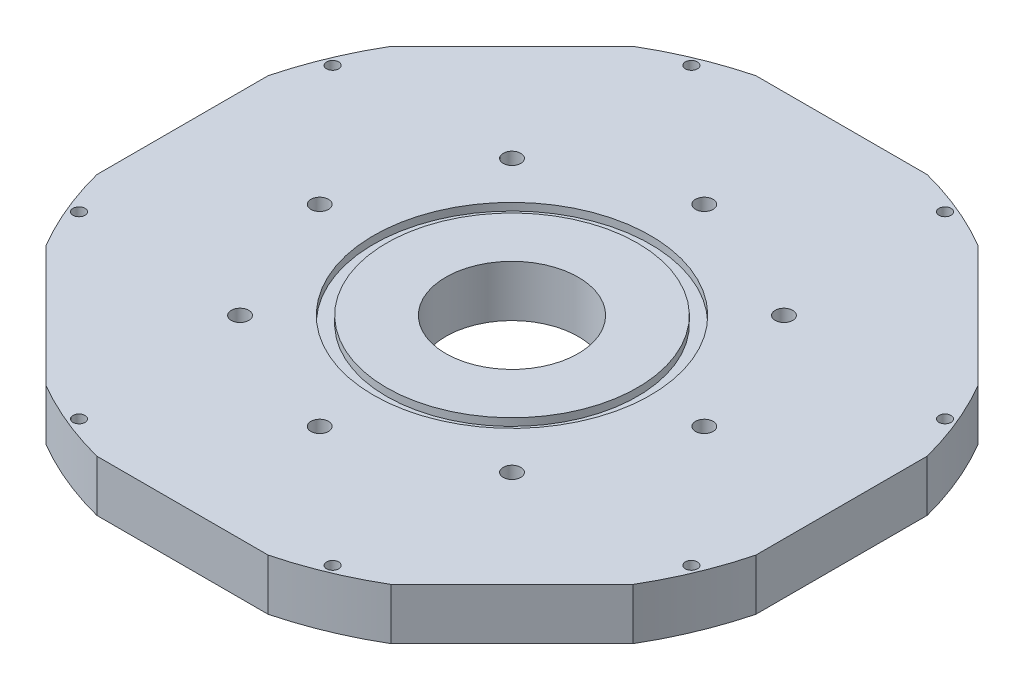
SolidWorks part; units mm, degrees
material "6061-T4 (SS)"
ref_plane "Front Plane" through (0, 0, 0) normal (0, 0, 1) x (1, 0, 0)
ref_plane "Top Plane" through (0, 0, 0) normal (0, 1, 0) x (1, 0, 0)
ref_plane "Right Plane" through (0, 0, 0) normal (1, 0, 0) x (0, 0, -1)
sketch "Sketch1" plane through (0, 0, 0) normal (0, 1, 0) x (1, 0, 0)
  line L1 (-50.6583, 122.3) -> (-122.3, 50.6583)
  line L2 (-122.3, 50.6583) -> (-122.3, -50.6583)
  line L3 (-122.3, -50.6583) -> (-50.6583, -122.3)
  line L4 (-50.6583, -122.3) -> (50.6583, -122.3)
  line L5 (50.6583, -122.3) -> (122.3, -50.6583)
  line L6 (122.3, -50.6583) -> (122.3, 50.6583)
  line L7 (122.3, 50.6583) -> (50.6583, 122.3)
  line L8 (50.6583, 122.3) -> (-50.6583, 122.3)
  circle A0 centre (0, 0) radius 122.3 construction
  circle A1 centre (0, 0) radius 126.365
  dimension "D2" = 252.73
  dimension "D1" = 244.6
extrude "Boss-Extrude1" add sketch "Sketch1" along normal blind 19.05 contours L4 A1 L5 L6 L7 L8 L1 L2 L3 region at (0, 0, 0)
sketch "Sketch3" plane through (0, 19.05, 0) normal (0, 1, 0) x (1, 0, 0)
  circle A0 centre (0, 0) radius 24.5745
  dimension "D1" = 49.149
extrude "Cut-Extrude1" cut sketch "Sketch3" against normal through all contours A0
sketch "Sketch5" plane through (0, 19.05, 0) normal (0, 1, 0) x (1, 0, 0)
  circle A0 centre (0, 0) radius 46.5455
  circle A1 centre (0, 0) radius 51.3715
  dimension "D1" = 93.091
  dimension "D2" = 102.743
extrude "Cut-Extrude2" cut sketch "Sketch5" against normal blind 2.794
sketch "Sketch19" plane through (0, 19.05, 0) normal (0, 1, 0) x (1, 0, 0)
  line L5 (-63.9978, 108.9605) -> (-31.7934, 122.3) construction
  line L6 (-47.8956, 115.6303) -> (-43.6974, 105.4949) construction
  circle A4 centre (0, 0) radius 122.9995
  circle A5 centre (-47.0699, 113.6367) radius 2.2479
  dimension "D1" = 4.4958
  dimension "D3" = 245.999
extrude "Cut-Extrude4" cut sketch "Sketch19" against normal through all contours A4 A5 | A4 A5 region at (-46.7034, 19.05, -112.7519) region at (-47.4335, 19.05, -114.5147)
pattern_circular "CirPattern2" count 8 over 360 about axis through (0, 0, 0) along (0, 1, 0) of "Cut-Extrude4"
sketch "Sketch21" plane through (0, 19.05, 0) normal (0, 1, 0) x (1, 0, 0)
  point P0 (-71.374, 0)
  dimension "D1" = 71.374
hole_wizard "5/16-18 Tapped Hole2" positions "Sketch22" profile "Sketch23" tap size "5/16-18" standard "ANSI Inch"
sketch "Sketch22" plane through (0, 19.05, 0) normal (0, 1, 0) x (1, 0, 0)
  point P0 (-71.374, 0)
sketch "Sketch23" plane through (-71.374, 19.05, 0) normal (1, 0, 0) x (0, 0, 1)
  line L0 (0, 0) -> (0, 14.6611)
  line L1 (0, 14.6611) -> (3.2639, 12.7)
  line L2 (3.2639, 12.7) -> (3.2639, 0)
  line L5 (3.2639, 0) -> (0, 0)
  line L10 (0, 14.6611) -> (-3.2639, 12.7) construction
  line L11 (0, -6.35) -> (0, 107.95) construction
  dimension "Tap Drill Dia." = 6.5278
  dimension "Tap Drill Depth" = 12.7
  dimension "Drill Angle" = 118
cosmetic thread "Hole Thread2" parameters "D1"=12.7, "D2"=7.9375
sketch "Sketch33" [suppressed] plane through (0, 19.05, 0) normal (0, 1, 0) x (1, 0, 0)
  circle A0 centre (-71.374, 0) radius 3.9687
  dimension "D1" = 7.9375
sketch "Sketch37" plane through (0, 0, 0) normal (0, -1, 0) x (1, 0, 0)
  circle A0 centre (0, 0) radius 119.0625
  circle A1 centre (0, 0) radius 115.2525
  dimension "D1" = 238.125
  dimension "D2" = 230.505
extrude "Cut-Extrude7" cut sketch "Sketch37" against normal blind 2.667
pattern_circular "CirPattern4" count 8 over 360 about axis through (0, 0, 0) along (0, 1, 0) of "5/16-18 Tapped Hole2" reverse direction yes
cosmetic thread "Hole Thread3" parameters "D1"=12.7, "D2"=7.9375
cosmetic thread "Hole Thread4" parameters "D1"=12.7, "D2"=7.9375
cosmetic thread "Hole Thread5" parameters "D1"=12.7, "D2"=7.9375
cosmetic thread "Hole Thread6" parameters "D1"=12.7, "D2"=7.9375
cosmetic thread "Hole Thread7" parameters "D1"=12.7, "D2"=7.9375
cosmetic thread "Hole Thread8" parameters "D1"=12.7, "D2"=7.9375
cosmetic thread "Hole Thread9" parameters "D1"=12.7, "D2"=7.9375
